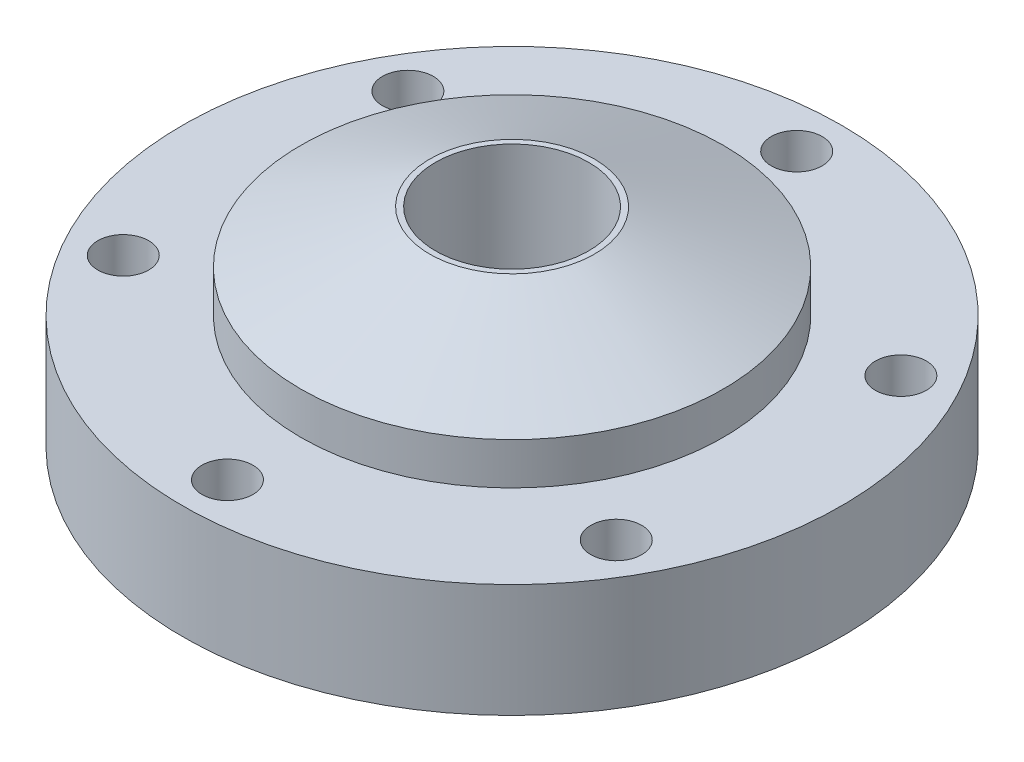
SolidWorks part; units mm, degrees
material "Nylon 6/10"
ref_plane "Front Plane" through (0, 0, 0) normal (0, 0, 1) x (1, 0, 0)
ref_plane "Top Plane" through (0, 0, 0) normal (0, 1, 0) x (1, 0, 0)
ref_plane "Right Plane" through (0, 0, 0) normal (1, 0, 0) x (0, 0, -1)
sketch "Sketch1" plane through (0, 0, 0) normal (0, 0, 1) x (1, 0, 0)
  line L0 (0, 0) -> (0, 11.9562) construction
  line L1 (5.12, 5) -> (5.12, 13.8632)
  line L2 (5.12, 13.8632) -> (5.5, 13.8632)
  line L3 (5.5, 13.8632) -> (14.1, 10.3613)
  line L4 (14.1, 10.3613) -> (14.1, 7.5673)
  line L5 (14.1, 7.5673) -> (22, 7.5673)
  line L6 (22, 7.5673) -> (22, 0)
  line L7 (22, 0) -> (6.75, 0)
  line L8 (5.12, 5) -> (6.75, 5)
  line L9 (6.75, 5) -> (6.75, 0)
  point P12 (14.1, 14.6524)
  point P13 (5.5, 19.4865)
  point P15 (14.1, 11.526)
  point P16 (24.5636, 7.5673)
  dimension "D1" = 10.24
  dimension "D2" = 5
  dimension "D3" = 13.5
  dimension "D4" = 28.2
  dimension "D5" = 11
  dimension "D6" = 2.794
  dimension "D7" = 13.8632
  dimension "D8" = 7.5673
  dimension "D9" = 44
revolve "Revolve1" add sketch "Sketch1" angle 360 about L0
sketch "Sketch2" plane through (0, 7.5673, 0) normal (0, 1, 0) x (1, 0, 0)
  point P0 (0, 19)
  point P1 (0, 0)
  point P2 (18.2918, 7.0607)
  point P3 (0, 0)
  point P4 (16.4545, 9.5)
  point P5 (16.4545, -9.5)
  point P6 (0, -19)
  point P7 (-16.4545, -9.5)
  point P8 (-16.4545, 9.5)
  point P9 (0, 0)
  point P11 (0, 0)
  point P12 (-14.5161, 8.3809)
  dimension "D2" = 38
  dimension "D1" = 6
hole_wizard "M3 Clearance Hole1" positions "Sketch2" profile "Sketch3" hole size "M3" standard "ANSI Metric" end condition up to next
sketch "Sketch3" plane through (0, 7.5673, -19) normal (1, 0, 0) x (0, 0, 1)
  line L0 (0, 0) -> (0, 7.5673)
  line L1 (0, 7.5673) -> (1.7, 7.5673)
  line L2 (1.7, 7.5673) -> (1.7, 0)
  line L5 (1.7, 0) -> (0, 0)
  line L11 (0, -6.35) -> (0, 107.95) construction
  dimension "Thru Hole Dia." = 3.4
  dimension "Thru Hole Depth" = 7.5673
